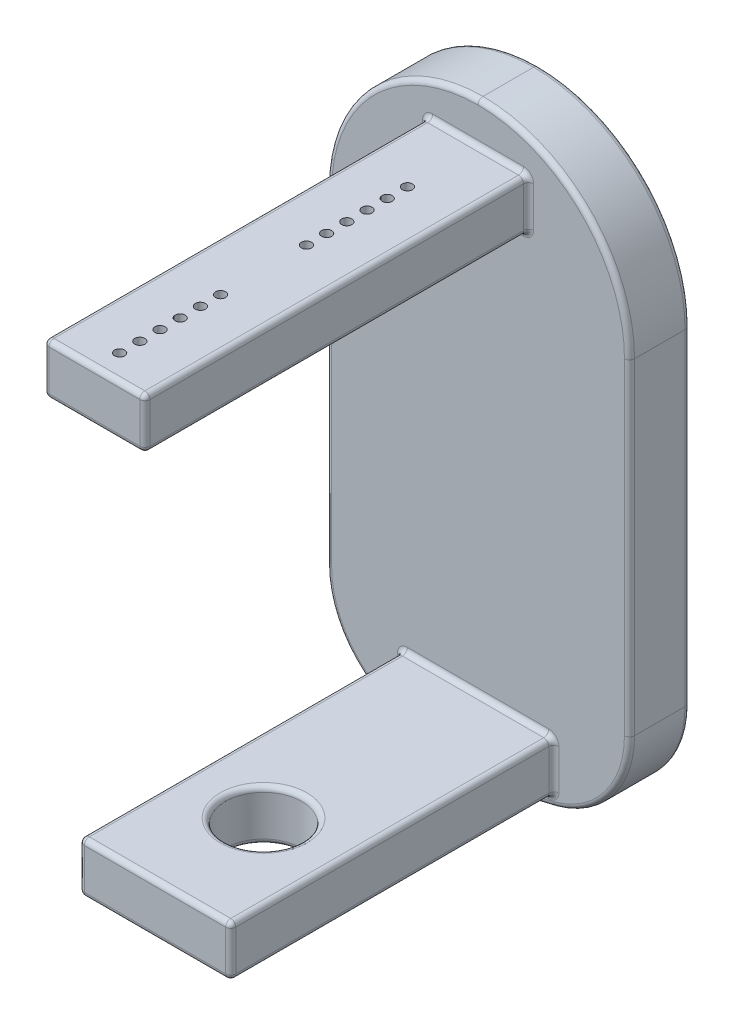
SolidWorks part; units mm, degrees
ref_plane "Front Plane" through (0, 0, 0) normal (0, 0, 1) x (1, 0, 0)
ref_plane "Top Plane" through (0, 0, 0) normal (0, 1, 0) x (1, 0, 0)
ref_plane "Right Plane" through (0, 0, 0) normal (1, 0, 0) x (0, 0, -1)
sketch "Sketch1" plane through (0, 0, 0) normal (0, 0, 1) x (1, 0, 0)
  circle A0 centre (0, 0) radius 29
  dimension "D1" = 58
extrude "Boss-Extrude1" add sketch "Sketch1" along normal blind 6
sketch "Sketch6" plane through (0, 0, 6) normal (0, 0, 1) x (1, 0, 0)
  line L0 (-15.0047, 24.8165) -> (-15.0047, -24.8165)
  line L1 (14.9953, 24.8222) -> (14.9953, -24.8222)
  arc A0 (-15.0047, 24.8165) -> (-15.0047, -24.8165) centre (0, 0) ccw
  circle A1 centre (0, 0) radius 29
  arc A2 (14.9953, -24.8222) -> (14.9953, 24.8222) centre (0, 0) ccw
  dimension "D2" = 15.0047
  dimension "D3" = 30
  dimension "D1" = 0
extrude "Cut-Extrude3" cut sketch "Sketch6" against normal blind 10
fillet "Fillet2" radius 15 2 edges at (-15.0047, 24.8165, 3) (14.9953, 24.8222, 3)
fillet "Fillet3" radius 10 2 edges at (-15.0047, -24.8165, 3) (14.9953, -24.8222, 3)
sketch "Sketch2" plane through (0, 0, 6) normal (0, 0, 1) x (1, 0, 0)
  line L1 (-5, 25) -> (5, 25)
  line L2 (-5, 25) -> (-5, 20)
  line L3 (-5, 20) -> (5, 20)
  line L4 (5, 25) -> (5, 20)
  line L5 (-5, 25) -> (5, 20) construction
  line L6 (-5, 20) -> (5, 25) construction
  point P0 (0, 22.5)
  dimension "D1" = 5
  dimension "D2" = 25
  dimension "D3" = 10
extrude "Boss-Extrude2" add sketch "Sketch2" along normal blind 38
sketch "Sketch3" plane through (0, 25, 0) normal (0, 1, 0) x (1, 0, 0)
  line L0 (5, -6) -> (-5, -6) construction
  line L1 (5, -44) -> (-5, -44) construction
  circle A0 centre (0, -13) radius 0.5
  circle A1 centre (0, -15) radius 0.5
  circle A2 centre (0, -17) radius 0.5
  circle A3 centre (0, -19) radius 0.5
  circle A4 centre (0, -21) radius 0.5
  circle A5 centre (0, -23) radius 0.5
  circle A6 centre (0, -41.5) radius 0.5
  circle A7 centre (0, -39.5) radius 0.5
  circle A8 centre (0, -37.5) radius 0.5
  circle A9 centre (0, -35.5) radius 0.5
  circle A10 centre (0, -33.5) radius 0.5
  circle A11 centre (0, -31.5) radius 0.5
  point P20 (0, -44)
  dimension "D2" = 1
  dimension "D5" = 8.5
  dimension "D6" = 2
  dimension "D1" = 7
  dimension "D7" = 2
  dimension "D3" = 6
  dimension "D4" = 6
extrude "Cut-Extrude1" cut sketch "Sketch3" against normal blind 5
sketch "Sketch4" plane through (0, 0, 6) normal (0, 0, 1) x (1, 0, 0)
  line L1 (-7.5, -22) -> (7.5, -22)
  line L2 (-7.5, -22) -> (-7.5, -27)
  line L3 (-7.5, -27) -> (7.5, -27)
  line L4 (7.5, -22) -> (7.5, -27)
  line L5 (-7.5, -22) -> (7.5, -27) construction
  line L6 (-7.5, -27) -> (7.5, -22) construction
  line L7 (-5, 20) -> (5, 20) construction
  point P0 (0, -24.5)
  dimension "D1" = 42
  dimension "D2" = 15
  dimension "D3" = 5
extrude "Boss-Extrude3" add sketch "Sketch4" along normal blind 32
sketch "Sketch5" plane through (0, -22, 0) normal (0, 1, 0) x (1, 0, 0)
  line L0 (-7.5, -6) -> (7.5, -6) construction
  circle A0 centre (0, -27.25) radius 3.8
  dimension "D1" = 21.25
  dimension "D2" = 7.6
extrude "Cut-Extrude2" cut sketch "Sketch5" against normal blind 28
fillet "Fillet4" radius 0.5 40 edges at (7.5, -22, 22) (0, -22, 38) (-7.5, -22, 22) (0, -22, 31.05) (-7.5, -27, 22) (0, -27, 38) (7.5, -27, 22) (0, -27, 31.05) (5, 20, 25) (-5, 20, 25) (0, 20, 44) (5, 25, 25) (0, 25, 44) (-5, 25, 25) (-7.5, -24.5, 6) (0, -27, 6) (7.5, -24.5, 6) (0, -22, 6) (-5, 22.5, 6) (0, 20, 6) (5, 22.5, 6) (0, 25, 6) (-10.6131, 24.6048, 6) (10.6001, 24.6084, 6) (14.9953, -2.1658, 6) (12.9417, -24.4024, 6) (-0.0075, -29, 6) (-12.9527, -24.3977, 6) (-15.0047, -2.1645, 6) (-7.5, -24.5, 38) (7.5, -24.5, 38) (-5, 22.5, 44) (5, 22.5, 44) (12.9417, -24.4024, 0) (14.9953, -2.1658, 0) (10.6001, 24.6084, 0) (-10.6131, 24.6048, 0) (-15.0047, -2.1645, 0) (-12.9527, -24.3977, 0) (-0.0075, -29, 0)
